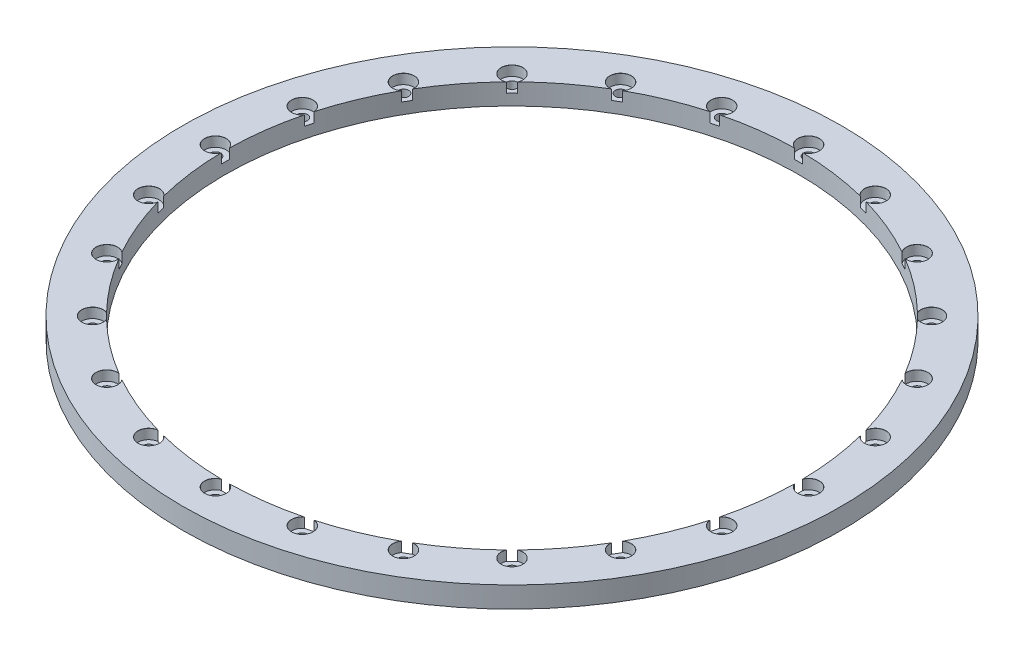
SolidWorks part; units mm, degrees
material "Delrin 2700 NC010, Low Viscosity Acetal Copolymer (SS)"
ref_plane "Front Plane" through (0, 0, 0) normal (0, 0, 1) x (1, 0, 0)
ref_plane "Top Plane" through (0, 0, 0) normal (0, 1, 0) x (1, 0, 0)
ref_plane "Right Plane" through (0, 0, 0) normal (1, 0, 0) x (0, 0, -1)
sketch "Sketch1" plane through (0, 0, 0) normal (0, 1, 0) x (1, 0, 0)
  circle A0 centre (0, 0) radius 100
  circle A1 centre (0, 0) radius 87
  dimension "D1" = 200
  dimension "D2" = 174
extrude "Boss-Extrude1" add sketch "Sketch1" along normal blind 6.35
hole_wizard "CBORE for M3 SHCS1" positions "Sketch2" profile "Sketch3" counterbore size "M3" standard "ANSI Metric" end condition through all
sketch "Sketch2" plane through (0, 6.35, 0) normal (0, 1, 0) x (1, 0, 0)
  line L0 (0, 0) -> (90, 0) construction
  point P0 (90, 0)
  point P15 (86.9333, -23.2937)
  point P16 (77.9423, -45)
  point P17 (63.6396, -63.6396)
  point P18 (45, -77.9423)
  point P19 (23.2937, -86.9333)
  point P20 (0, -90)
  point P21 (-23.2937, -86.9333)
  point P22 (-45, -77.9423)
  point P23 (-63.6396, -63.6396)
  point P24 (-77.9423, -45)
  point P25 (-86.9333, -23.2937)
  point P26 (-90, 0)
  point P27 (-86.9333, 23.2937)
  point P28 (-77.9423, 45)
  point P29 (-63.6396, 63.6396)
  point P30 (-45, 77.9423)
  point P31 (-23.2937, 86.9333)
  point P32 (0, 90)
  point P33 (23.2937, 86.9333)
  point P34 (45, 77.9423)
  point P35 (63.6396, 63.6396)
  point P36 (77.9423, 45)
  point P37 (86.9333, 23.2937)
  dimension "D1" = 90
  dimension "D2" = 24
sketch "Sketch3" plane through (90, 6.35, 0) normal (1, 0, 0) x (0, 0, 1)
  line L0 (0, 0) -> (0, 6.35)
  line L1 (0, 6.35) -> (1.6, 6.35)
  line L3 (1.6, 6.35) -> (1.6, 3)
  line L4 (3.25, 3) -> (1.6, 3)
  line L5 (3.25, 3) -> (3.25, 0.025)
  line L6 (3.25, 0.025) -> (3.275, 0)
  line L7 (3.275, 0) -> (0, 0)
  line L8 (-3.25, 0.025) -> (-3.275, 0) construction
  line L11 (0, -6.35) -> (0, 107.95) construction
  dimension "Thru Hole Dia." = 3.2
  dimension "Thru Hole Depth" = 6.35
  dimension "C'Bore Dia." = 6.5
  dimension "C'Bore Depth" = 3
  dimension "Near C'Sink Dia." = 6.55
  dimension "Near C'Sink Angle" = 90
